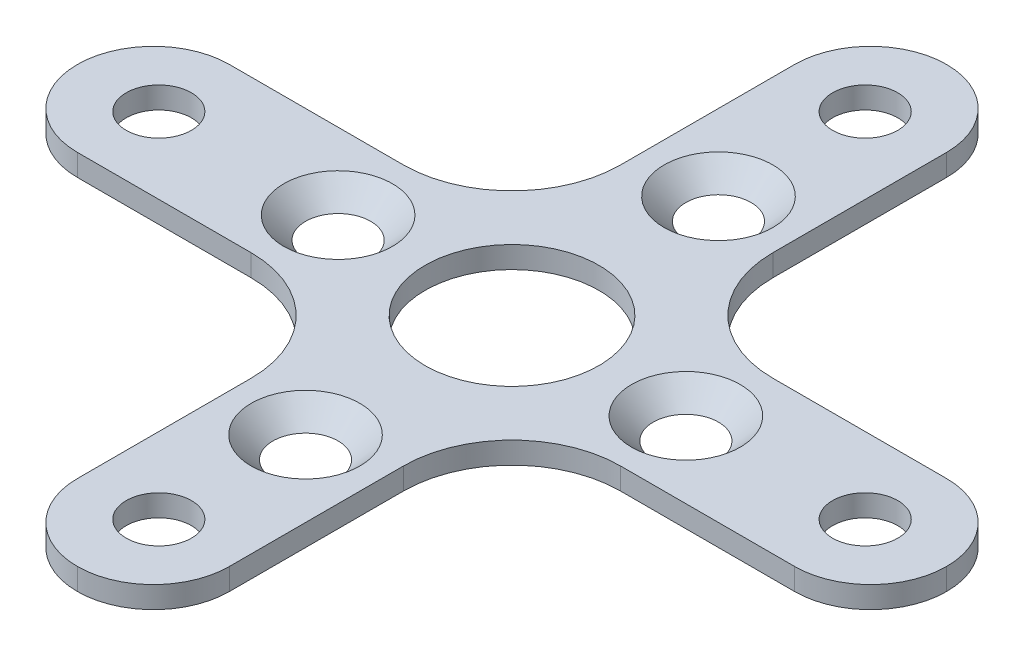
SolidWorks part; units mm, degrees
ref_plane "Front Plane" through (0, 0, 0) normal (0, 0, 1) x (1, 0, 0)
ref_plane "Top Plane" through (0, 0, 0) normal (0, 1, 0) x (1, 0, 0)
ref_plane "Right Plane" through (0, 0, 0) normal (1, 0, 0) x (0, 0, -1)
sketch "Sketch1" plane through (0, 0, 0) normal (0, 1, 0) x (1, 0, 0)
  line L0 (0, -20) -> (0, 20)
  line L1 (-3.5, 20) -> (3.5, 20)
  line L2 (-3.5, 20) -> (-3.5, -20)
  line L3 (-3.5, -20) -> (3.5, -20)
  line L4 (3.5, 20) -> (3.5, -20)
  line L5 (-3.5, 20) -> (3.5, -20) construction
  line L6 (-3.5, -20) -> (3.5, 20) construction
  line L7 (-20, 3.5) -> (20, 3.5)
  line L8 (-20, 3.5) -> (-20, -3.5)
  line L9 (-20, -3.5) -> (20, -3.5)
  line L10 (20, 3.5) -> (20, -3.5)
  line L11 (-20, 3.5) -> (20, -3.5) construction
  line L12 (-20, -3.5) -> (20, 3.5) construction
  line L13 (-20, 0) -> (20, 0)
  circle A1 centre (0, 16.25) radius 1.5
  circle A2 centre (0, 9.5) radius 1.5
  circle A3 centre (0, -9.5) radius 1.5
  circle A4 centre (0, -16.25) radius 1.5
  circle A5 centre (-16.25, 0) radius 1.5
  circle A6 centre (-8, 0) radius 1.5
  circle A7 centre (8, 0) radius 1.5
  circle A8 centre (16.25, 0) radius 1.5
  point P0 (0, 0)
  point P6 (0, 0)
  dimension "D3" = 3
  dimension "D4" = 3
  dimension "D13" = 3
  dimension "D14" = 3
  dimension "D15" = 3
  dimension "D16" = 3
  dimension "D17" = 3
  dimension "D18" = 3
  dimension "D1" = 40
  dimension "D2" = 7
  dimension "D5" = 9.5
  dimension "D6" = 16.25
  dimension "D7" = 16.25
  dimension "D8" = 16.25
  dimension "D9" = 16.25
  dimension "D10" = 9.5
  dimension "D11" = 8
  dimension "D12" = 8
extrude "Boss-Extrude1" add sketch "Sketch1" along normal blind 1 contours A6 L13 L2 L7 L8 A5 | A6 L13 A5 L8 L9 L2 | A2 L0 A1 L1 L2 L7 | A2 L0 L7 L4 L1 A1 | A8 L13 L10 L7 L4 A7 | L2 L13 L0 L7 | L13 L2 L9 L0 | L13 L0 L9 L4 | L0 L13 L4 L7 | A4 L0 A3 L9 L2 L3 | A4 L0 L3 L4 L9 A3 | A8 L13 A7 L4 L9 L10 region at (-1.9053, 0, 11.5931) region at (1.9053, 0, 11.5931) region at (-11.6977, 0, 1.9053) region at (-1.75, 0, 1.75) region at (1.75, 0, 1.75) region at (11.6977, 0, 1.9053) region at (-11.6977, 0, -1.9053) region at (-1.75, 0, -1.75) region at (1.75, 0, -1.75) region at (11.6977, 0, -1.9053) region at (-1.9053, 0, -11.5931) region at (1.9053, 0, -11.5931)
fillet "Fillet1" radius 5 4 edges at (-3.5, 0.5, -3.5) (3.5, 0.5, -3.5) (3.5, 0.5, 3.5) (-3.5, 0.5, 3.5)
fillet "Fillet2" radius 3.5 8 edges at (20, 0.5, 3.5) (20, 0.5, -3.5) (3.5, 0.5, -20) (-3.5, 0.5, -20) (-20, 0.5, -3.5) (-20, 0.5, 3.5) (3.5, 0.5, 20) (-3.5, 0.5, 20)
sketch "Sketch2" plane through (0, 1, 0) normal (0, 1, 0) x (1, 0, 0)
  circle A0 centre (0, 0) radius 4
  dimension "D1" = 8
extrude "Cut-Extrude1" cut sketch "Sketch2" against normal up to next
chamfer "Chamfer1" distance 1 4 edges at (0, 1, 11) (0, 1, -8) (8, 1, 1.5) (-8, 1, 1.5)
